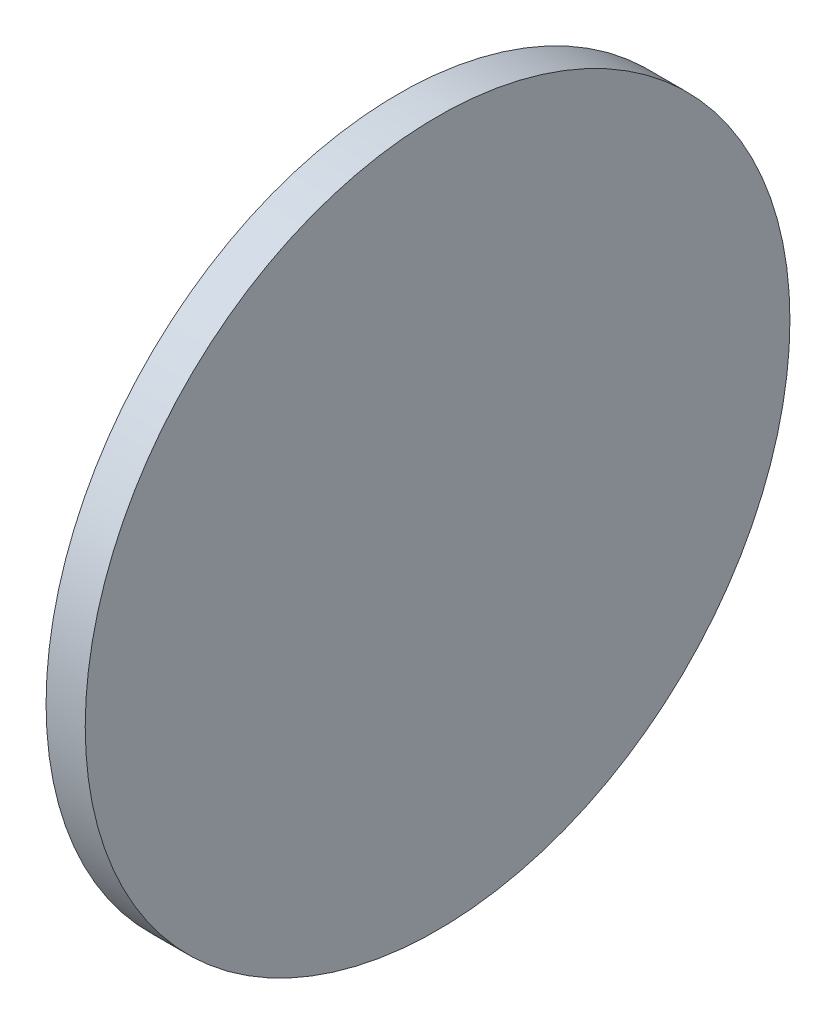
SolidWorks part; units mm, degrees
material "7075-T6 (SN)"
ref_plane "Front Plane" through (0, 0, 0) normal (0, 0, 1) x (1, 0, 0)
ref_plane "Top Plane" through (0, 0, 0) normal (0, 1, 0) x (1, 0, 0)
ref_plane "Right Plane" through (0, 0, 0) normal (1, 0, 0) x (0, 0, -1)
sketch "Sketch1" plane through (0, 0, 0) normal (1, 0, 0) x (0, 0, -1)
  circle A0 centre (0, 0) radius 57.15
  dimension "D1" = 114.3
extrude "Boss-Extrude1" add sketch "Sketch1" along normal blind 6.35
sketch "Sketch2" plane through (0, 0, 0) normal (-1, 0, 0) x (0, 0, 1)
  circle A0 centre (0, 0) radius 45.847
  dimension "D1" = 91.694
extrude "Boss-Extrude2" add sketch "Sketch2" along normal blind 6.35
